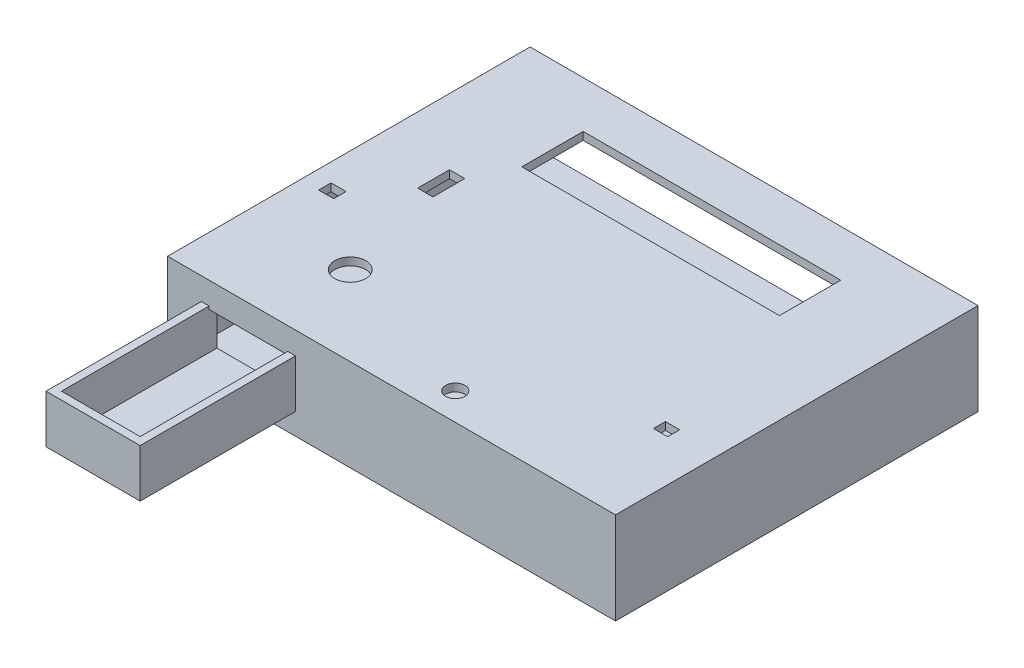
SolidWorks part; units mm, degrees
ref_plane "Front Plane" through (0, 0, 0) normal (0, 0, 1) x (1, 0, 0)
ref_plane "Top Plane" through (0, 0, 0) normal (0, 1, 0) x (1, 0, 0)
ref_plane "Right Plane" through (0, 0, 0) normal (1, 0, 0) x (0, 0, -1)
sketch "Sketch1" plane through (0, 0, 0) normal (0, 0, 1) x (1, 0, 0)
  line L0 (0, 0) -> (173, 0)
  line L1 (0, 0) -> (0, 35.5199)
  line L2 (0, 35.5199) -> (173, 35.5199)
  line L3 (173, 35.5199) -> (173, 0)
extrude "Boss-Extrude2" add sketch "Sketch1" along normal blind 140
shell "Shell3" thickness 3 removed face at (86.5, 17.7599, 0)
sketch "Sketch3" plane through (0, 35.5199, 0) normal (0, 1, 0) x (1, 0, 0)
  line L0 (173, -140) -> (173, 0) construction
  line L1 (38.5, -18) -> (138, -18)
  line L2 (38.5, -18) -> (38.5, -41.7)
  line L3 (38.5, -41.7) -> (138, -41.7)
  line L4 (138, -18) -> (138, -41.7)
  line L5 (0, -140) -> (0, 0) construction
  line L6 (173, 0) -> (0, 0) construction
  line L8 (25.5, -56.6351) -> (31.4, -56.6351)
  line L9 (25.5, -56.6351) -> (25.5, -68.9351)
  line L10 (25.5, -68.9351) -> (31.4, -68.9351)
  line L11 (31.4, -56.6351) -> (31.4, -68.9351)
  line L14 (7.0099, -83.8904) -> (12.8103, -83.8904)
  line L15 (7.0099, -83.8904) -> (7.0099, -88.6904)
  line L16 (7.0099, -88.6904) -> (12.8103, -88.6904)
  line L17 (12.8103, -83.8904) -> (12.8103, -88.6904)
  line L19 (156.9349, -99.1576) -> (151.4349, -99.1576)
  line L20 (156.9349, -99.1576) -> (156.9349, -103.8055)
  line L21 (156.9349, -103.8055) -> (151.4349, -103.8055)
  line L22 (151.4349, -99.1576) -> (151.4349, -103.8055)
  circle A0 centre (39.737, -109.2007) radius 6
  circle A1 centre (100.5675, -129.4644) radius 3.7
  point P4 (138, -29.85)
  dimension "D1" = 99.5
  dimension "D2" = 35
  dimension "D3" = 38.5
  dimension "D4" = 18
  dimension "D5" = 23.7
  dimension "D6" = 25.5
  dimension "D7" = 12.3
  dimension "D8" = 5.9
  dimension "D9" = 5.8004
  dimension "D10" = 4.8
extrude "Cut-Extrude3" cut sketch "Sketch3" against normal blind 7.5 contours L9 L8 L11 L10 | L15 L14 L17 L16 | L2 L1 L4 L3 | A0 | A1 | L20 L19 L22 L21
sketch "Sketch5" plane through (0, 0, 140) normal (0, 0, 1) x (1, 0, 0)
  line L1 (13.0298, 26.8918) -> (49.3913, 26.8918)
  line L2 (13.0298, 26.8918) -> (13.0298, 8.296)
  line L3 (13.0298, 8.296) -> (49.3913, 8.296)
  line L4 (49.3913, 26.8918) -> (49.3913, 8.296)
extrude "Boss-Extrude4" add sketch "Sketch5" along normal blind 60
shell "Shell5" thickness 3 removed face at (31.2106, 26.8918, 170)
sketch "Sketch8" plane through (0, 0, 140) normal (0, 0, 1) x (1, 0, 0)
  line L0 (16.0298, 26.8918) -> (16.0298, 11.296) construction
  line L1 (16.0298, 25.7185) -> (46.3913, 25.7185)
  line L2 (16.0298, 25.7185) -> (16.0298, 11.296)
  line L3 (16.0298, 11.296) -> (46.3913, 11.296)
  line L4 (46.3913, 25.7185) -> (46.3913, 11.296)
  line L5 (16.0298, 11.296) -> (46.3913, 11.296) construction
extrude "Cut-Extrude6" cut sketch "Sketch8" against normal blind 20.5
